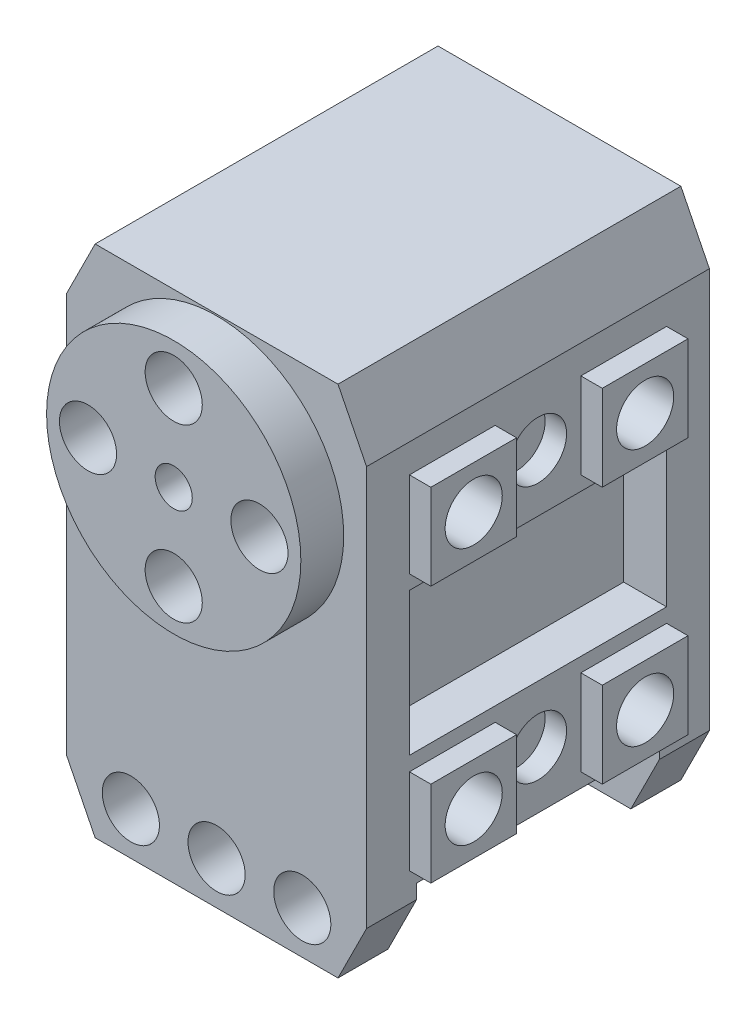
SolidWorks part; units mm, degrees
ref_plane "Front Plane" through (0, 0, 0) normal (0, 0, 1) x (1, 0, 0)
ref_plane "Top Plane" through (0, 0, 0) normal (0, 1, 0) x (1, 0, 0)
ref_plane "Right Plane" through (0, 0, 0) normal (1, 0, 0) x (0, 0, -1)
sketch "Sketch1" plane through (0, 0, 0) normal (0, 0, 1) x (1, 0, 0)
  line L1 (-10.5, 18) -> (10.5, 18)
  line L2 (-10.5, 18) -> (-10.5, -18)
  line L3 (-10.5, -18) -> (10.5, -18)
  line L4 (10.5, 18) -> (10.5, -18)
  line L5 (0, -18) -> (0, 18) construction
  line L6 (-10.5, 0) -> (10.5, 0) construction
  circle A0 centre (0, 9) radius 8.9
  point P0 (0, 0)
  dimension "D3" = 17.8
  dimension "D1" = 36
  dimension "D2" = 21
  dimension "D4" = 9
extrude "Boss-Extrude1" add sketch "Sketch1" along normal blind 24
extrude "Boss-Extrude2" add sketch "Sketch1<2>" along normal blind 27 contours A0 region at (0, 9, 0)
sketch "Sketch1<2>" plane through (0, 0, 0) normal (0, 0, 1) x (1, 0, 0) same geometry as "Sketch1"
sketch "Sketch2" plane through (0, 0, 27) normal (0, 0, 1) x (1, 0, 0)
  circle A0 centre (0, 9) radius 6
  circle A1 centre (0, 15) radius 2
  circle A2 centre (6, 9) radius 2
  circle A3 centre (0, 9) radius 6
  circle A4 centre (0, 3) radius 2
  circle A5 centre (0, 9) radius 6
  circle A6 centre (-6, 9) radius 2
  circle A7 centre (0, 9) radius 6
  circle A8 centre (0, 9) radius 1.3
  point P17 (0, 9)
  dimension "D1" = 12
  dimension "D2" = 4
  dimension "D4" = 2.6
  dimension "D3" = 4
extrude "Cut-Extrude1" cut sketch "Sketch2" against normal blind 3 contours A5 A6 | A5 A6 | A0 A1 | A0 A1 | A0 A2 | A0 A2 | A3 A4 | A3 A4 | A8 region at (5.094, 9, 27) region at (6.786, 9, 27) region at (0, 14.094, 27) region at (0, 15.786, 27) region at (0, 2.214, 27) region at (0, 3.906, 27) region at (-5.094, 9, 27) region at (-6.786, 9, 27) region at (0, 9, 27)
chamfer "Chamfer1" distance 4 distance2 2 2 edges at (-10.5, -18, 12) (10.5, 18, 12) first distance on face at (-10.5, 0, 12) first distance on face at (10.5, 0, 12)
chamfer "Chamfer2" distance 2 distance2 4 2 edges at (-10.5, 18, 12) (10.5, -18, 12) first distance on face at (-1, 18, 12) first distance on face at (1, -18, 12)
sketch "Sketch4" plane through (0, 0, 24) normal (0, 0, 1) x (1, 0, 0)
  line L0 (8.5, 18) -> (-8.5, 18) construction
  circle A0 centre (0, -15) radius 2
  circle A1 centre (-6, -15) radius 2
  circle A2 centre (6, -15) radius 2
  dimension "D1" = 4
  dimension "D2" = 33
  dimension "D3" = 4
  dimension "D4" = 4
  dimension "D5" = 12
  dimension "D6" = 6
extrude "Cut-Extrude2" cut sketch "Sketch4" against normal through all both and the other way through all
sketch "Sketch5" plane through (-10.5, 0, 0) normal (-1, 0, 0) x (0, 0, 1)
  line L0 (0, 18) -> (24, 18) construction
  line L1 (3.5, -25.5518) -> (20.5, -25.5518)
  line L2 (3.5, -25.5518) -> (3.5, -13)
  line L3 (3.5, -13) -> (20.5, -13)
  line L4 (20.5, -25.5518) -> (20.5, -13)
  point P6 (12, -13)
  point P7 (12, 18)
  dimension "D1" = 31
  dimension "D2" = 17
  dimension "D3" = 0
extrude "Cut-Extrude3" cut sketch "Sketch5" against normal through all both and the other way through all
sketch "Sketch7" plane through (10.5, 0, 0) normal (1, 0, 0) x (0, 0, -1)
  line L0 (0, 14) -> (-24, 14) construction
  line L1 (-21, 12) -> (-15, 12)
  line L2 (-21, 12) -> (-21, 6)
  line L3 (-21, 6) -> (-15, 6)
  line L4 (-15, 12) -> (-15, 6)
  line L5 (-18, 6) -> (-18, 12) construction
  line L6 (-21, 9) -> (-15, 9) construction
  line L7 (-9, 12) -> (-3, 12)
  line L8 (-9, 12) -> (-9, 6)
  line L9 (-9, 6) -> (-3, 6)
  line L10 (-3, 12) -> (-3, 6)
  line L11 (-6, 6) -> (-6, 12) construction
  line L12 (-9, 9) -> (-3, 9) construction
  line L13 (-9, -6) -> (-3, -6)
  line L14 (-9, -6) -> (-9, -12)
  line L15 (-9, -12) -> (-3, -12)
  line L16 (-3, -6) -> (-3, -12)
  line L17 (-6, -12) -> (-6, -6) construction
  line L18 (-9, -9) -> (-3, -9) construction
  line L19 (-21, -6) -> (-15, -6)
  line L20 (-21, -6) -> (-21, -12)
  line L21 (-21, -12) -> (-15, -12)
  line L22 (-15, -6) -> (-15, -12)
  line L23 (-18, -12) -> (-18, -6) construction
  line L24 (-21, -9) -> (-15, -9) construction
  point P0 (0, 0)
  point P4 (-6, 9)
  point P25 (0, 0)
  point P26 (-12, 14)
  point P28 (0, 0)
  point P32 (0, 0)
  dimension "D1" = 6
  dimension "D2" = 6
  dimension "D3" = 6
  dimension "D4" = 6
  dimension "D5" = 12
  dimension "D6" = 18
  dimension "D7" = 6
extrude "Boss-Extrude3" add sketch "Sketch7" along normal blind 1.5
extrude "Boss-Extrude4" add sketch "Sketch7<2>" against normal blind 1.5 from surface starting at face at (-10.5, -6.75, 12)
sketch "Sketch7<2>" plane through (10.5, 0, 0) normal (1, 0, 0) x (0, 0, -1) same geometry as "Sketch7"
sketch "Sketch6" plane through (10.5, 0, 0) normal (1, 0, 0) x (0, 0, -1)
  line L0 (-24, 18) -> (0, 18) construction
  circle A0 centre (-12, 9) radius 2
  circle A1 centre (-6, 9) radius 2
  circle A2 centre (-18, 9) radius 2
  circle A3 centre (-12, -9) radius 2
  circle A4 centre (-6, -9) radius 2
  circle A5 centre (-18, -9) radius 2
  point P4 (-12, 18)
  point P7 (0, 0)
  point P16 (0, 0)
  point P17 (-12, -9)
  point P18 (0, 0)
  point P19 (0, 0)
  dimension "D1" = 4
  dimension "D5" = 4
  dimension "D6" = 4
  dimension "D2" = 9
  dimension "D3" = 0
  dimension "D4" = 6
  dimension "D7" = 6
  dimension "D8" = 18
  dimension "D9" = 12
  dimension "D10" = 6
extrude "Cut-Extrude6" cut sketch "Sketch6" against normal blind 3 from surface starting at face at (12, 9, 6)
extrude "Cut-Extrude7" cut sketch "Sketch6<3>" along normal blind 3 from surface starting at face at (-12, 9, 18)
sketch "Sketch6<3>" plane through (10.5, 0, 0) normal (1, 0, 0) x (0, 0, -1) same geometry as "Sketch6"
sketch "Sketch8" plane through (10.5, 0, 0) normal (1, 0, 0) x (0, 0, -1)
  line L1 (-21, 5) -> (-3, 5)
  line L2 (-21, 5) -> (-21, -5)
  line L3 (-21, -5) -> (-3, -5)
  line L4 (-3, 5) -> (-3, -5)
  line L5 (-12, -5) -> (-12, 5) construction
  line L6 (-21, 0) -> (-3, 0) construction
  line L7 (-20.5, -13) -> (-3.5, -13) construction
  point P0 (-12, 0)
  point P4 (0, 0)
  point P5 (0, 0)
  point P13 (-12, -13)
  dimension "D1" = 10
  dimension "D2" = 18
extrude "Cut-Extrude8" cut sketch "Sketch8" against normal blind 3
extrude "Cut-Extrude9" cut sketch "Sketch8<2>" along normal blind 3 from surface starting at face at (-10.5, -9, 10)
sketch "Sketch8<2>" plane through (10.5, 0, 0) normal (1, 0, 0) x (0, 0, -1) same geometry as "Sketch8"
